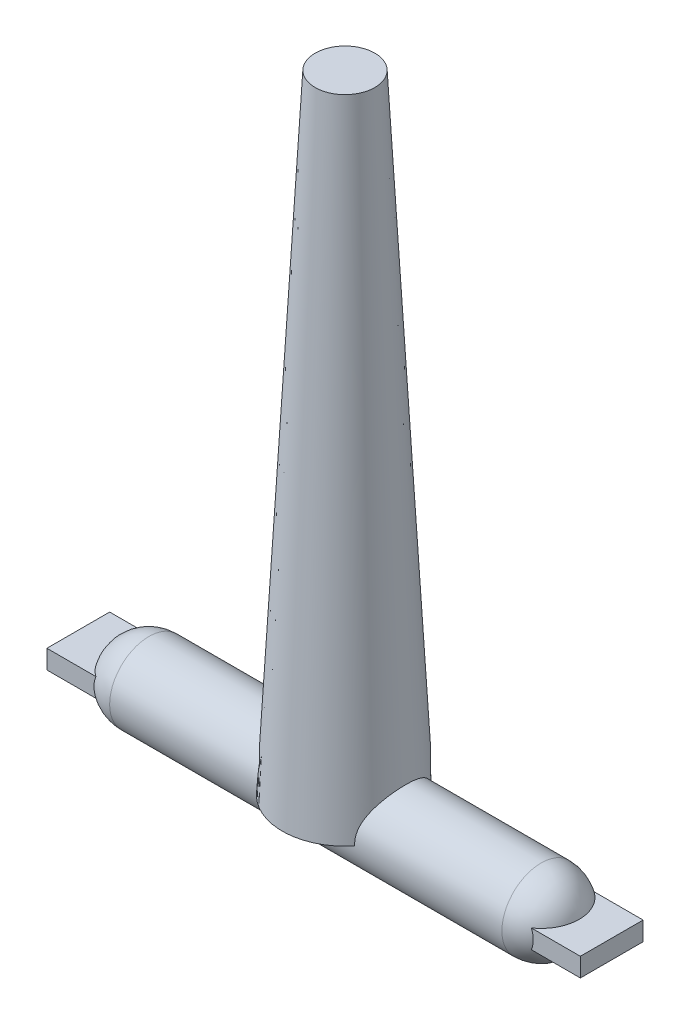
SolidWorks part; units mm, degrees
material "ABS"
ref_plane "Front" through (0, 0, 0) normal (0, 0, 1) x (1, 0, 0)
ref_plane "Top" through (0, 0, 0) normal (0, 1, 0) x (1, 0, 0)
ref_plane "Right" through (0, 0, 0) normal (1, 0, 0) x (0, 0, -1)
sketch "Sketch1" plane through (0, 0, 0) normal (0, 0, 1) x (1, 0, 0)
  line L0 (0, 50.8) -> (0, 0)
  line L1 (0, 0) -> (5.0753, 0)
  line L2 (5.0753, 0) -> (2.413, 50.8)
  line L3 (2.413, 50.8) -> (0, 50.8)
  dimension "D1" = 2.413
  dimension "D2" = 3
  dimension "D3" = 50.8
revolve "Revolve1" add sketch "Sketch1" angle 360 about L0
sketch "Sketch3" plane through (0, 0, 0) normal (1, 0, 0) x (0, 0, -1)
  circle A0 centre (0, 0) radius 3.175
  dimension "D1" = 6.35
extrude "Boss-Extrude1" add sketch "Sketch3" along normal mid plane 38.1
fillet "Fillet1" radius 3.175 2 edges at (-19.05, 0, -3.175) (19.05, 0, -3.175)
sketch "Sketch4" plane through (0, 0, 0) normal (1, 0, 0) x (0, 0, -1)
  line L1 (-2.54, 0.762) -> (2.54, 0.762)
  line L2 (-2.54, 0.762) -> (-2.54, -0.762)
  line L3 (-2.54, -0.762) -> (2.54, -0.762)
  line L4 (2.54, 0.762) -> (2.54, -0.762)
  point P4 (-2.54, 0)
  point P6 (0, 0.762)
  dimension "D1" = 5.08
  dimension "D2" = 1.524
extrude "Boss-Extrude2" add sketch "Sketch4" along normal mid plane 43.18
